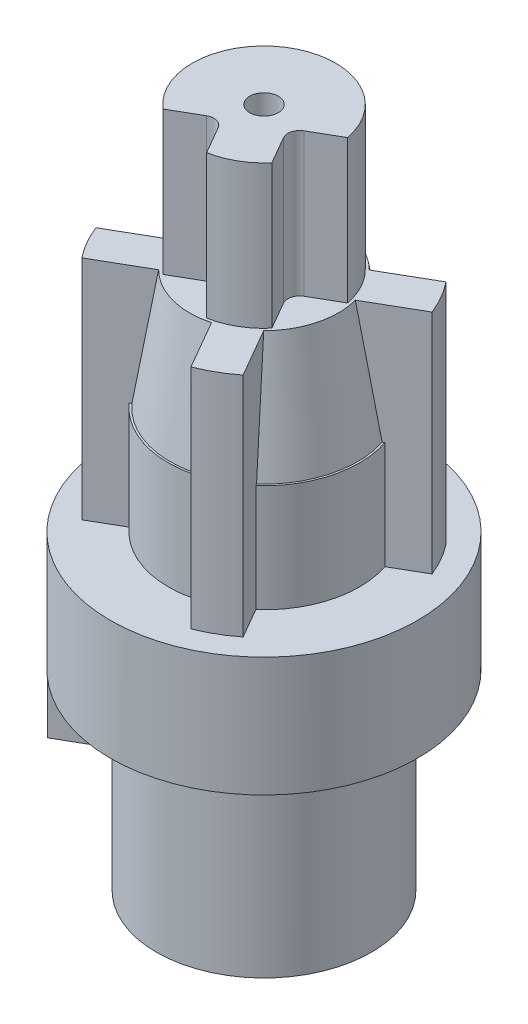
SolidWorks part; units mm, degrees
ref_plane "Front Plane" through (0, 0, 0) normal (0, 0, 1) x (1, 0, 0)
ref_plane "Top Plane" through (0, 0, 0) normal (0, 1, 0) x (1, 0, 0)
ref_plane "Right Plane" through (0, 0, 0) normal (1, 0, 0) x (0, 0, -1)
sketch "Sketch1" plane through (0, 0, 0) normal (0, 1, 0) x (1, 0, 0)
  circle A0 centre (0, 0) radius 4.5
  circle A1 centre (0, 0) radius 3.25
  dimension "D1" = 9
  dimension "D2" = 6.5
extrude "Boss-Extrude1" add sketch "Sketch1" along normal blind 8
sketch "Sketch2" plane through (0, 8, 0) normal (0, 1, 0) x (1, 0, 0)
  line L0 (0, 0) -> (-4.5, 0) construction
  line L1 (0, 0) -> (-3.8971, -2.25) construction
  line L2 (-0.4, 0.6928) -> (-6.7372, -2.9659) construction
  line L3 (0.4, -0.6928) -> (-5.8033, -4.2743) construction
  line L4 (-0.4, 0.6928) -> (-4.2971, -1.5572) construction
  line L5 (0.4, -0.6928) -> (-3.4971, -2.9428) construction
  line L6 (-4.235, -1.5213) -> (-3.435, -2.907) construction
  line L7 (-4.235, -1.5213) -> (-5.9671, -2.5213)
  line L8 (-5.9671, -2.5213) -> (-5.1671, -3.907)
  line L9 (-5.1671, -3.907) -> (-3.435, -2.907)
  line L10 (-4.235, -1.5213) -> (-3.435, -2.907)
  circle A0 centre (0, 0) radius 4.5 construction
  dimension "D1" = 30
  dimension "D4" = 2
  dimension "D2" = 0.8
  dimension "D3" = 0.8
extrude "Boss-Extrude2" add sketch "Sketch2" against normal blind 3.1
sketch "Sketch3" plane through (0, 8, 0) normal (0, 1, 0) x (1, 0, 0)
  arc A0 (-3.435, -2.907) -> (-4.235, -1.5213) centre (0, 0) ccw construction
  circle A1 centre (0, 0) radius 4.5
  circle A2 centre (0, 0) radius 3.25 construction
  circle A3 centre (0, 0) radius 3.25
extrude "Boss-Extrude3" add sketch "Sketch3" along normal blind 5
sketch "Sketch4" plane through (0, 13, 0) normal (0, 1, 0) x (1, 0, 0)
  line L0 (-4.3308, -1.2224) -> (-1.4084, 4.2739) construction
  line L1 (0.5011, -3.2111) -> (2.9424, 1.3802)
  line L2 (0, 0) -> (-4.5, 0) construction
  line L3 (0.2605, -3.6636) -> (3.183, 1.8327) construction
  circle A0 centre (0, 0) radius 3.25 construction
  circle A1 centre (0, 0) radius 4.5
  circle A2 centre (0, 0) radius 4.5
  circle A3 centre (0, 0) radius 3.25
  circle A4 centre (0, 0) radius 4.5 construction
  circle M6 centre (0, 0) radius 3.25
  dimension "D3" = 62
  dimension "D1" = 0
  dimension "D2" = 5.2
extrude "Boss-Extrude4" add sketch "Sketch4" against normal blind 8 contours L1 M6
sketch "Sketch11" plane through (0, 8, 0) normal (0, 1, 0) x (1, 0, 0)
  line L0 (-5.9671, -2.5213) -> (-5.1671, -3.907) construction
  circle A0 centre (0, 0) radius 6.4283
  circle A1 centre (0, 0) radius 4.5 construction
  circle A2 centre (0, 0) radius 4.5
  arc M2 (-3.435, -2.907) -> (-4.235, -1.5213) centre (0, 0) cw
  line M3 (-4.235, -1.5213) -> (-5.9671, -2.5213)
  line M5 (-5.1671, -3.907) -> (-3.435, -2.907)
extrude "Boss-Extrude11" add sketch "Sketch11" along normal up to surface (5 mm away) contours A2 A0 M5 M3 | A0 M3 M5 M2 up to face at (0, 13, 4.5)
sketch "Sketch12" plane through (0, 13, 0) normal (0, 1, 0) x (1, 0, 0)
  line L1 (0.5011, -3.2111) -> (2.9424, 1.3802)
  line L2 (0.5011, -3.2111) -> (2.9424, 1.3802)
  circle A0 centre (0, 0) radius 6.4283 construction
  arc A1 (2.9424, 1.3802) -> (0.5011, -3.2111) centre (0, 0) ccw
  arc A2 (2.9424, 1.3802) -> (0.5011, -3.2111) centre (0, 0) ccw
  circle A3 centre (0, 0) radius 6.4283
  circle A4 centre (0, 0) radius 5.4283
  arc M4 (0.5011, -3.2111) -> (2.9424, 1.3802) centre (0, 0) cw
  line M5 (2.9424, 1.3802) -> (0.5011, -3.2111)
  dimension "D1" = 0
  dimension "D2" = 1
extrude "Boss-Extrude12" add sketch "Sketch12" along normal blind 5.5 contours A4 M5 M4
sketch "Sketch14" plane through (0, 18.5, 0) normal (0, 1, 0) x (1, 0, 0)
  circle A0 centre (0, 0) radius 6.4283 construction
  circle A7 centre (0, 0) radius 6.4283
extrude "Boss-Extrude13" add sketch "Sketch14" along normal blind 4
sketch "Sketch18" plane through (0, 22.5, 0) normal (0, 1, 0) x (1, 0, 0)
  line L3 (-4.235, -1.5213) -> (-5.9671, -2.5213) construction
  line L4 (-5.1238, -3.882) -> (-2.9941, -2.6524)
  line L5 (-3.7941, -1.2668) -> (-5.9238, -2.4964)
  line L6 (-3.7941, -1.2668) -> (-2.9941, -2.6524) construction
  line L7 (-3.3941, -1.9596) -> (0, 0) construction
  line L8 (-1.2668, 3.7941) -> (-2.4964, 5.9238)
  line L9 (-3.882, 5.1238) -> (-2.6524, 2.9941)
  line L10 (-1.9596, 3.3941) -> (0, 0) construction
  line L11 (-1.2668, 3.7941) -> (-2.6524, 2.9941) construction
  line L12 (3.7941, 1.2668) -> (5.9238, 2.4964)
  line L13 (5.1238, 3.882) -> (2.9941, 2.6524)
  line L14 (3.3941, 1.9596) -> (0, 0) construction
  line L15 (3.7941, 1.2668) -> (2.9941, 2.6524) construction
  line L16 (1.2668, -3.7941) -> (2.4964, -5.9238)
  line L17 (3.882, -5.1238) -> (2.6524, -2.9941)
  line L18 (1.9596, -3.3941) -> (0, 0) construction
  line L19 (1.2668, -3.7941) -> (2.6524, -2.9941) construction
  line L20 (0, 0) -> (-3.3941, -1.9596) construction
  circle A0 centre (0, 0) radius 4
  arc A1 (-2.4964, 5.9238) -> (-3.882, 5.1238) centre (0, 0) ccw
  circle A2 centre (0, 0) radius 6.4283
  arc A3 (-5.9238, -2.4964) -> (-5.1238, -3.882) centre (0, 0) ccw
  arc A4 (5.9238, 2.4964) -> (5.1238, 3.882) centre (0, 0) ccw
  arc A5 (2.4964, -5.9238) -> (3.882, -5.1238) centre (0, 0) ccw
  circle A6 centre (0, 0) radius 6.4283 construction
  circle A7 centre (0, 0) radius 6.4283
  circle A8 centre (0, 0) radius 5.4283 construction
  circle A9 centre (0, 0) radius 5.4283
  circle M6 centre (0, 0) radius 6.4283
  dimension "D1" = 8
  dimension "D4" = 3.9192
  dimension "D2" = 0
  dimension "D3" = 4
extrude "Cut-Extrude6" cut sketch "Sketch18" against normal up to surface (9.5 mm away) contours L13 A9 L8 A0 | A9 L13 L8 M6 | L17 A9 L12 A0 | A9 L17 L12 M6 | A9 L12 L13 M6 | L9 A9 L5 A0 | A9 L9 L5 M6 | A9 L8 L9 M6 | A9 L5 L4 M6 | A9 L4 L16 M6 | L4 A9 L16 A0 | A9 L16 L17 M6
sketch "Sketch19" plane through (0, 22.5, -28.5) normal (0, -1, 0) x (-1, 0, 0)
  line L8 (-2.9495, -27.9518) -> (-1.366, -28.866)
  line L9 (-1.366, -28.866) -> (-2.2802, -30.4495)
  line L10 (-0.5482, -31.4495) -> (0.366, -29.866)
  line L11 (0.366, -29.866) -> (1.9495, -30.7802)
  line L12 (-5.0497, -26.5083) -> (-3.7941, -27.2332)
  line L13 (-2.9941, -25.8476) -> (-4.2497, -25.1227)
  line L14 (1.9917, -23.4503) -> (1.2668, -24.7059)
  line L15 (2.6524, -25.5059) -> (3.3773, -24.2503)
  line L16 (5.0497, -30.4917) -> (3.7941, -29.7668)
  line L17 (2.9941, -31.1524) -> (4.2497, -31.8773)
  line L18 (-1.9917, -33.5497) -> (-1.2668, -32.2941)
  line L19 (-2.6524, -31.4941) -> (-3.3773, -32.7497)
  line L20 (-5.0497, -26.5083) -> (-3.7941, -27.2332)
  line L21 (-2.9941, -25.8476) -> (-4.2497, -25.1227)
  line L22 (1.9917, -23.4503) -> (1.2668, -24.7059)
  line L23 (2.6524, -25.5059) -> (3.3773, -24.2503)
  line L24 (5.0497, -30.4917) -> (3.7941, -29.7668)
  line L25 (2.9941, -31.1524) -> (4.2497, -31.8773)
  line L26 (-1.9917, -33.5497) -> (-1.2668, -32.2941)
  line L27 (-2.6524, -31.4941) -> (-3.3773, -32.7497)
  arc A4 (1.9495, -30.7802) -> (-2.9495, -27.9518) centre (0, -28.5) ccw
  arc A5 (-2.2802, -30.4495) -> (-0.5482, -31.4495) centre (0, -28.5) ccw
  arc A10 (-4.2497, -25.1227) -> (-5.0497, -26.5083) centre (0, -28.5) ccw
  arc A11 (1.2668, -24.7059) -> (-2.9941, -25.8476) centre (0, -28.5) ccw
  arc A12 (3.3773, -24.2503) -> (1.9917, -23.4503) centre (0, -28.5) ccw
  arc A13 (3.7941, -29.7668) -> (2.6524, -25.5059) centre (0, -28.5) ccw
  arc A14 (4.2497, -31.8773) -> (5.0497, -30.4917) centre (0, -28.5) ccw
  arc A15 (-1.2668, -32.2941) -> (2.9941, -31.1524) centre (0, -28.5) ccw
  arc A16 (-3.3773, -32.7497) -> (-1.9917, -33.5497) centre (0, -28.5) ccw
  arc A17 (-3.7941, -27.2332) -> (-2.6524, -31.4941) centre (0, -28.5) ccw
  arc A18 (-4.2497, -25.1227) -> (-5.0497, -26.5083) centre (0, -28.5) ccw
  arc A19 (1.2668, -24.7059) -> (-2.9941, -25.8476) centre (0, -28.5) ccw
  arc A20 (3.3773, -24.2503) -> (1.9917, -23.4503) centre (0, -28.5) ccw
  arc A21 (3.7941, -29.7668) -> (2.6524, -25.5059) centre (0, -28.5) ccw
  arc A22 (4.2497, -31.8773) -> (5.0497, -30.4917) centre (0, -28.5) ccw
  arc A23 (-1.2668, -32.2941) -> (2.9941, -31.1524) centre (0, -28.5) ccw
  arc A24 (-3.3773, -32.7497) -> (-1.9917, -33.5497) centre (0, -28.5) ccw
  arc A25 (-3.7941, -27.2332) -> (-2.6524, -31.4941) centre (0, -28.5) ccw
  dimension "D1" = 3
  dimension "D3" = 1
  dimension "D4" = 2
  dimension "D2" = 0
extrude "Boss-Extrude14" add sketch "Sketch19" against normal blind 6 contours A5 L9 L8 A4 L11 L10
ref_plane "Plane1" through (0, 0, 0) normal (0.866, 0, -0.5) x (-0.5, 0, -0.866)
sketch "Sketch29" plane through (0, 0, 0) normal (0.866, 0, -0.5) x (-0.5, 0, -0.866)
  line L2 (-3.1192, 22.5) -> (-3.9192, 17.5)
  line L3 (0, 0) -> (0, 28.5) construction
  line L9 (3, 28.5) -> (-1, 28.5) construction
  line L10 (-3.9192, 17.5) -> (-4.6441, 17.5)
  line L11 (-4.6441, 17.5) -> (-4.6441, 22.5)
  line L12 (-5.369, 22.5) -> (-3.9192, 22.5) construction
  line L13 (-4.6441, 22.5) -> (-3.9192, 22.5)
  line L14 (-3.9192, 13) -> (-3.9192, 22.5) construction
  line L15 (-0.8, 22.5) -> (-3.9192, 22.5) construction
  line L16 (-3.9192, 22.5) -> (-3.1192, 22.5)
  dimension "D2" = 0.8
  dimension "D1" = 5
revolve "Cut-Revolve3" cut sketch "Sketch29" angle 360 about L3
sketch "Sketch30" plane through (0, 17.5, 0) normal (0, 1, 0) x (1, 0, 0)
  line L8 (3.5618, 2.9802) -> (2.9941, 2.6524)
  line L9 (-1.2668, 3.7941) -> (-1.5945, 4.3618)
  line L10 (-2.9802, 3.5618) -> (-2.6524, 2.9941)
  line L11 (-3.7941, -1.2668) -> (-4.3618, -1.5945)
  line L12 (-3.5618, -2.9802) -> (-2.9941, -2.6524)
  line L13 (1.2668, -3.7941) -> (1.5945, -4.3618)
  line L14 (2.9802, -3.5618) -> (2.6524, -2.9941)
  line L15 (3.7941, 1.2668) -> (4.3618, 1.5945)
  line L16 (3.5618, 2.9802) -> (0.2928, 1.0928)
  line L17 (2.6524, -2.9941) -> (-1.5945, 4.3618)
  line L18 (-2.9802, 3.5618) -> (1.2668, -3.7941)
  line L19 (-1.0928, 0.2928) -> (-4.3618, -1.5945)
  line L20 (-3.5618, -2.9802) -> (-0.2928, -1.0928)
  line L21 (1.2668, -3.7941) -> (1.5945, -4.3618)
  line L22 (2.9802, -3.5618) -> (2.6524, -2.9941)
  line L23 (1.0928, -0.2928) -> (4.3618, 1.5945)
  arc A8 (4.3618, 1.5945) -> (3.5618, 2.9802) centre (0, 0) ccw
  arc A9 (2.9941, 2.6524) -> (-1.2668, 3.7941) centre (0, 0) ccw
  arc A10 (-1.5945, 4.3618) -> (-2.9802, 3.5618) centre (0, 0) ccw
  arc A11 (-2.6524, 2.9941) -> (-3.7941, -1.2668) centre (0, 0) ccw
  arc A12 (-4.3618, -1.5945) -> (-3.5618, -2.9802) centre (0, 0) ccw
  arc A13 (-2.9941, -2.6524) -> (1.2668, -3.7941) centre (0, 0) ccw
  arc A14 (1.5945, -4.3618) -> (2.9802, -3.5618) centre (0, 0) ccw
  arc A15 (2.6524, -2.9941) -> (3.7941, 1.2668) centre (0, 0) ccw
  arc A16 (4.3618, 1.5945) -> (3.5618, 2.9802) centre (0, 0) ccw
  arc A18 (-1.5945, 4.3618) -> (-2.9802, 3.5618) centre (0, 0) ccw
  arc A20 (-4.3618, -1.5945) -> (-3.5618, -2.9802) centre (0, 0) ccw
  arc A22 (1.5945, -4.3618) -> (2.9802, -3.5618) centre (0, 0) ccw
  circle M17 centre (0, 0) radius 3.9192
  arc M18 (4.3618, 1.5945) -> (3.5618, 2.9802) centre (0, 0) ccw
  line M19 (3.5618, 2.9802) -> (2.9941, 2.6524)
  line M21 (-1.2668, 3.7941) -> (-1.5945, 4.3618)
  arc M22 (-1.5945, 4.3618) -> (-2.9802, 3.5618) centre (0, 0) ccw
  line M23 (-2.9802, 3.5618) -> (-2.6524, 2.9941)
  line M25 (-3.7941, -1.2668) -> (-4.3618, -1.5945)
  arc M26 (-4.3618, -1.5945) -> (-3.5618, -2.9802) centre (0, 0) ccw
  line M27 (-3.5618, -2.9802) -> (-2.9941, -2.6524)
  line M29 (1.2668, -3.7941) -> (1.5945, -4.3618)
  arc M30 (1.5945, -4.3618) -> (2.9802, -3.5618) centre (0, 0) ccw
  line M31 (2.9802, -3.5618) -> (2.6524, -2.9941)
  line M33 (3.7941, 1.2668) -> (4.3618, 1.5945)
  dimension "D1" = 0
extrude "Boss-Extrude15" add sketch "Sketch30" along normal up to surface (5 mm away) contours L20 L18 L19 M17 | L17 L23 L16 M17 | L18 L17 M17 | L23 L16 M17 M33 M18 M19 | L20 L19 M27 M17 M25 M26 | L18 L17 M23 M17 M21 M22 | L18 L17 M17 M29 M30 M31 up to face at (-4.3336, 22.5, 2.502)
sketch "Sketch31" plane through (0, 0, 0) normal (0, -1, 0) x (1, 0, 0)
  circle A0 centre (0, 0) radius 0.6
  dimension "D1" = 1.2
extrude "Cut-Extrude7" cut sketch "Sketch31" against normal through all both and the other way through all
fillet "Fillet1" radius 0.5 2 edges at (-0.366, 25.5, 1.366) (1.366, 25.5, 0.366)
